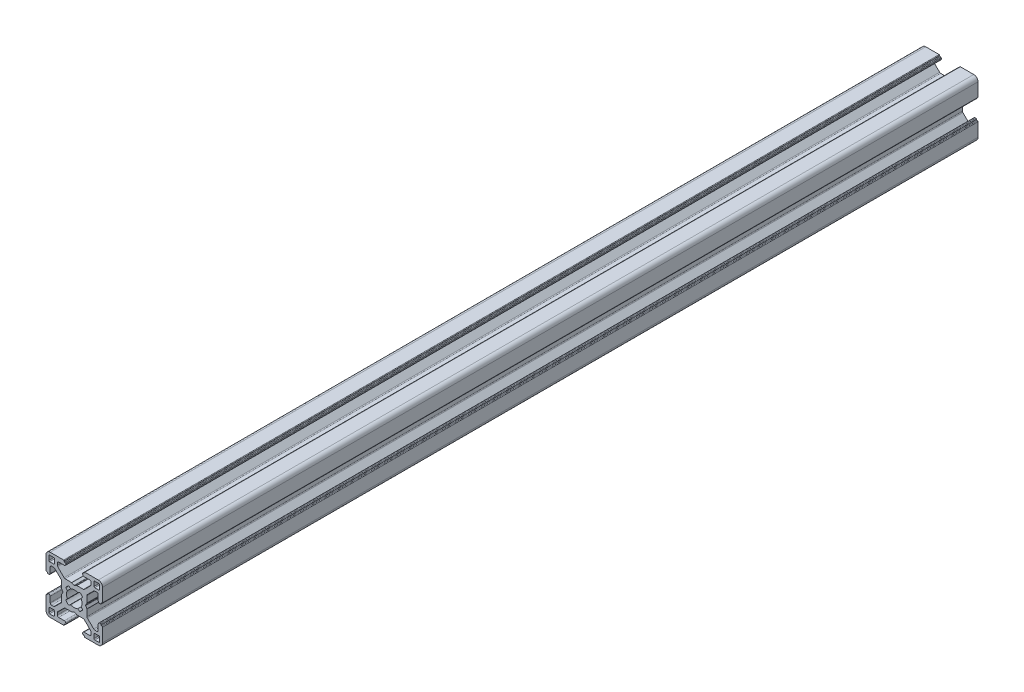
SolidWorks part; units mm, degrees
material "6063-O, Barra estrusa (SS)"
ref_plane "Piano frontale" through (0, 0, 0) normal (0, 0, 1) x (1, 0, 0)
ref_plane "Piano superiore" through (0, 0, 0) normal (0, 1, 0) x (1, 0, 0)
ref_plane "Piano destro" through (0, 0, 0) normal (1, 0, 0) x (0, 0, -1)
ref_plane "Piano1" through (0, 0, 100) normal (0, 0, 1) x (1, 0, 0)
sketch "Schizzo1" plane through (0, 0, 100) normal (0, 0, 1) x (1, 0, 0)
  line L0 (-1.9139, 2.9896) -> (-1.2582, 2.4453)
  line L1 (1.2582, 2.4453) -> (1.9139, 2.9896)
  line L2 (2.9922, 1.9099) -> (2.4453, 1.2582)
  line L3 (2.4453, -1.2582) -> (2.9922, -1.9099)
  line L4 (1.9139, -2.9896) -> (1.2582, -2.4453)
  line L5 (-1.2582, -2.4453) -> (-1.9139, -2.9896)
  line L6 (-2.9922, -1.9099) -> (-2.4453, -1.2582)
  line L7 (-2.4453, 1.2582) -> (-2.9922, 1.9099)
  line L8 (-9.3, 3) -> (-9, 3)
  line L9 (-8.5, 3.5) -> (-8.5, 5.5)
  line L10 (-8, 6) -> (-7.2678, 6)
  line L11 (-6.9142, 5.8536) -> (-4.6464, 3.5858)
  line L12 (-4.5, 3.2322) -> (-4.5, 0.9536)
  line L13 (-4.4732, 0.8536) -> (-4.0381, 0.1)
  line L14 (-4.0381, -0.1) -> (-4.4732, -0.8536)
  line L15 (-4.5, -0.9536) -> (-4.5, -3.2322)
  line L16 (-4.6464, -3.5858) -> (-6.9142, -5.8536)
  line L17 (-7.2678, -6) -> (-8, -6)
  line L18 (-8.5, -5.5) -> (-8.5, -3.5)
  line L19 (-9, -3) -> (-9.3, -3)
  line L20 (-9.5, -3.2) -> (-9.5, -3.35)
  line L21 (-9.7, -3.55) -> (-9.8, -3.55)
  line L22 (-10, -3.75) -> (-10, -8.5)
  line L23 (-8.5, -10) -> (-3.75, -10)
  line L24 (-3.55, -9.8) -> (-3.55, -9.7)
  line L25 (-3.35, -9.5) -> (-3.2, -9.5)
  line L26 (-3, -9.3) -> (-3, -9)
  line L27 (-3.5, -8.5) -> (-5.5, -8.5)
  line L28 (-6, -8) -> (-6, -7.2678)
  line L29 (-5.8536, -6.9142) -> (-3.5858, -4.6464)
  line L30 (-3.2322, -4.5) -> (-0.9536, -4.5)
  line L31 (-0.8536, -4.4732) -> (-0.1, -4.0381)
  line L32 (0.1, -4.0381) -> (0.8536, -4.4732)
  line L33 (0.9536, -4.5) -> (3.2322, -4.5)
  line L34 (3.5858, -4.6464) -> (5.8536, -6.9142)
  line L35 (6, -7.2678) -> (6, -8)
  line L36 (5.5, -8.5) -> (3.5, -8.5)
  line L37 (3, -9) -> (3, -9.3)
  line L38 (3.2, -9.5) -> (3.35, -9.5)
  line L39 (3.55, -9.7) -> (3.55, -9.8)
  line L40 (3.75, -10) -> (8.5, -10)
  line L41 (10, -8.5) -> (10, -3.75)
  line L42 (9.8, -3.55) -> (9.7, -3.55)
  line L43 (9.5, -3.35) -> (9.5, -3.2)
  line L44 (9.3, -3) -> (9, -3)
  line L45 (8.5, -3.5) -> (8.5, -5.5)
  line L46 (8, -6) -> (7.2678, -6)
  line L47 (6.9142, -5.8536) -> (4.6464, -3.5858)
  line L48 (4.5, -3.2322) -> (4.5, -0.9536)
  line L49 (4.4732, -0.8536) -> (4.0381, -0.1)
  line L50 (4.0381, 0.1) -> (4.4732, 0.8536)
  line L51 (4.5, 0.9536) -> (4.5, 3.2322)
  line L52 (4.6464, 3.5858) -> (6.9142, 5.8536)
  line L53 (7.2678, 6) -> (8, 6)
  line L54 (8.5, 5.5) -> (8.5, 3.5)
  line L55 (9, 3) -> (9.3, 3)
  line L56 (9.5, 3.2) -> (9.5, 3.35)
  line L57 (9.7, 3.55) -> (9.8, 3.55)
  line L58 (10, 3.75) -> (10, 8.5)
  line L59 (8.5, 10) -> (3.75, 10)
  line L60 (3.55, 9.8) -> (3.55, 9.7)
  line L61 (3.35, 9.5) -> (3.2, 9.5)
  line L62 (3, 9.3) -> (3, 9)
  line L63 (3.5, 8.5) -> (5.5, 8.5)
  line L64 (6, 8) -> (6, 7.2678)
  line L65 (5.8536, 6.9142) -> (3.5858, 4.6464)
  line L66 (3.2322, 4.5) -> (0.9536, 4.5)
  line L67 (0.8536, 4.4732) -> (0.1, 4.0381)
  line L68 (-0.1, 4.0381) -> (-0.8536, 4.4732)
  line L69 (-0.9536, 4.5) -> (-3.2322, 4.5)
  line L70 (-3.5858, 4.6464) -> (-5.8536, 6.9142)
  line L71 (-6, 7.2678) -> (-6, 8)
  line L72 (-5.5, 8.5) -> (-3.5, 8.5)
  line L73 (-3, 9) -> (-3, 9.3)
  line L74 (-3.2, 9.5) -> (-3.35, 9.5)
  line L75 (-3.55, 9.7) -> (-3.55, 9.8)
  line L76 (-3.75, 10) -> (-8.5, 10)
  line L77 (-10, 8.5) -> (-10, 3.75)
  line L78 (-9.8, 3.55) -> (-9.7, 3.55)
  line L79 (-9.5, 3.35) -> (-9.5, 3.2)
  line L80 (8.7, 7) -> (7.3, 7)
  line L81 (-7.3, 7) -> (-8.7, 7)
  line L82 (-7, 7.3) -> (-7, 8.7)
  line L83 (-7.3, 9) -> (-8.7, 9)
  line L84 (-9, 7.3) -> (-9, 8.7)
  line L85 (9, 7.3) -> (9, 8.7)
  line L86 (8.7, 9) -> (7.3, 9)
  line L87 (7, 7.3) -> (7, 8.7)
  line L88 (8.7, -9) -> (7.3, -9)
  line L89 (9, -8.7) -> (9, -7.3)
  line L90 (8.7, -7) -> (7.3, -7)
  line L91 (7, -8.7) -> (7, -7.3)
  line L92 (-7.3, -9) -> (-8.7, -9)
  line L93 (-7, -8.7) -> (-7, -7.3)
  line L94 (-7.3, -7) -> (-8.7, -7)
  line L95 (-9, -8.7) -> (-9, -7.3)
  arc A0 (-1.2582, 2.4453) -> (1.2582, 2.4453) centre (0, 0) cw
  arc A1 (1.9139, 2.9896) -> (2.9922, 1.9099) centre (0, 0) cw
  arc A2 (2.4453, 1.2582) -> (2.4453, -1.2582) centre (0, 0) cw
  arc A3 (2.9922, -1.9099) -> (1.9139, -2.9896) centre (0, 0) cw
  arc A4 (1.2582, -2.4453) -> (-1.2582, -2.4453) centre (0, 0) cw
  arc A5 (-1.9139, -2.9896) -> (-2.9922, -1.9099) centre (0, 0) cw
  arc A6 (-2.4453, -1.2582) -> (-2.4453, 1.2582) centre (0, 0) cw
  arc A7 (-2.9922, 1.9099) -> (-1.9139, 2.9896) centre (0, 0) cw
  arc A8 (-9.5, 3.2) -> (-9.3, 3) centre (-9.3, 3.2) ccw
  arc A9 (-9, 3) -> (-8.5, 3.5) centre (-9, 3.5) ccw
  arc A10 (-8.5, 5.5) -> (-8, 6) centre (-8, 5.5) cw
  arc A11 (-7.2678, 6) -> (-6.9142, 5.8536) centre (-7.2678, 5.5) cw
  arc A12 (-4.6464, 3.5858) -> (-4.5, 3.2322) centre (-5, 3.2322) cw
  arc A13 (-4.5, 0.9536) -> (-4.4732, 0.8536) centre (-4.3, 0.9536) ccw
  arc A14 (-4.0381, 0.1) -> (-4.0381, -0.1) centre (-4.2113, 0) cw
  arc A15 (-4.4732, -0.8536) -> (-4.5, -0.9536) centre (-4.3, -0.9536) ccw
  arc A16 (-4.5, -3.2322) -> (-4.6464, -3.5858) centre (-5, -3.2322) cw
  arc A17 (-6.9142, -5.8536) -> (-7.2678, -6) centre (-7.2678, -5.5) cw
  arc A18 (-8, -6) -> (-8.5, -5.5) centre (-8, -5.5) cw
  arc A19 (-8.5, -3.5) -> (-9, -3) centre (-9, -3.5) ccw
  arc A20 (-9.3, -3) -> (-9.5, -3.2) centre (-9.3, -3.2) ccw
  arc A21 (-9.5, -3.35) -> (-9.7, -3.55) centre (-9.7, -3.35) cw
  arc A22 (-9.8, -3.55) -> (-10, -3.75) centre (-9.8, -3.75) ccw
  arc A23 (-10, -8.5) -> (-8.5, -10) centre (-8.5, -8.5) ccw
  arc A24 (-3.75, -10) -> (-3.55, -9.8) centre (-3.75, -9.8) ccw
  arc A25 (-3.55, -9.7) -> (-3.35, -9.5) centre (-3.35, -9.7) cw
  arc A26 (-3.2, -9.5) -> (-3, -9.3) centre (-3.2, -9.3) ccw
  arc A27 (-3, -9) -> (-3.5, -8.5) centre (-3.5, -9) ccw
  arc A28 (-5.5, -8.5) -> (-6, -8) centre (-5.5, -8) cw
  arc A29 (-6, -7.2678) -> (-5.8536, -6.9142) centre (-5.5, -7.2678) cw
  arc A30 (-3.5858, -4.6464) -> (-3.2322, -4.5) centre (-3.2322, -5) cw
  arc A31 (-0.9536, -4.5) -> (-0.8536, -4.4732) centre (-0.9536, -4.3) ccw
  arc A32 (-0.1, -4.0381) -> (0.1, -4.0381) centre (0, -4.2113) cw
  arc A33 (0.8536, -4.4732) -> (0.9536, -4.5) centre (0.9536, -4.3) ccw
  arc A34 (3.2322, -4.5) -> (3.5858, -4.6464) centre (3.2322, -5) cw
  arc A35 (5.8536, -6.9142) -> (6, -7.2678) centre (5.5, -7.2678) cw
  arc A36 (6, -8) -> (5.5, -8.5) centre (5.5, -8) cw
  arc A37 (3.5, -8.5) -> (3, -9) centre (3.5, -9) ccw
  arc A38 (3, -9.3) -> (3.2, -9.5) centre (3.2, -9.3) ccw
  arc A39 (3.35, -9.5) -> (3.55, -9.7) centre (3.35, -9.7) cw
  arc A40 (3.55, -9.8) -> (3.75, -10) centre (3.75, -9.8) ccw
  arc A41 (8.5, -10) -> (10, -8.5) centre (8.5, -8.5) ccw
  arc A42 (10, -3.75) -> (9.8, -3.55) centre (9.8, -3.75) ccw
  arc A43 (9.7, -3.55) -> (9.5, -3.35) centre (9.7, -3.35) cw
  arc A44 (9.5, -3.2) -> (9.3, -3) centre (9.3, -3.2) ccw
  arc A45 (9, -3) -> (8.5, -3.5) centre (9, -3.5) ccw
  arc A46 (8.5, -5.5) -> (8, -6) centre (8, -5.5) cw
  arc A47 (7.2678, -6) -> (6.9142, -5.8536) centre (7.2678, -5.5) cw
  arc A48 (4.6464, -3.5858) -> (4.5, -3.2322) centre (5, -3.2322) cw
  arc A49 (4.5, -0.9536) -> (4.4732, -0.8536) centre (4.3, -0.9536) ccw
  arc A50 (4.0381, -0.1) -> (4.0381, 0.1) centre (4.2113, 0) cw
  arc A51 (4.4732, 0.8536) -> (4.5, 0.9536) centre (4.3, 0.9536) ccw
  arc A52 (4.5, 3.2322) -> (4.6464, 3.5858) centre (5, 3.2322) cw
  arc A53 (6.9142, 5.8536) -> (7.2678, 6) centre (7.2678, 5.5) cw
  arc A54 (8, 6) -> (8.5, 5.5) centre (8, 5.5) cw
  arc A55 (8.5, 3.5) -> (9, 3) centre (9, 3.5) ccw
  arc A56 (9.3, 3) -> (9.5, 3.2) centre (9.3, 3.2) ccw
  arc A57 (9.5, 3.35) -> (9.7, 3.55) centre (9.7, 3.35) cw
  arc A58 (9.8, 3.55) -> (10, 3.75) centre (9.8, 3.75) ccw
  arc A59 (10, 8.5) -> (8.5, 10) centre (8.5, 8.5) ccw
  arc A60 (3.75, 10) -> (3.55, 9.8) centre (3.75, 9.8) ccw
  arc A61 (3.55, 9.7) -> (3.35, 9.5) centre (3.35, 9.7) cw
  arc A62 (3.2, 9.5) -> (3, 9.3) centre (3.2, 9.3) ccw
  arc A63 (3, 9) -> (3.5, 8.5) centre (3.5, 9) ccw
  arc A64 (5.5, 8.5) -> (6, 8) centre (5.5, 8) cw
  arc A65 (6, 7.2678) -> (5.8536, 6.9142) centre (5.5, 7.2678) cw
  arc A66 (3.5858, 4.6464) -> (3.2322, 4.5) centre (3.2322, 5) cw
  arc A67 (0.9536, 4.5) -> (0.8536, 4.4732) centre (0.9536, 4.3) ccw
  arc A68 (0.1, 4.0381) -> (-0.1, 4.0381) centre (0, 4.2113) cw
  arc A69 (-0.8536, 4.4732) -> (-0.9536, 4.5) centre (-0.9536, 4.3) ccw
  arc A70 (-3.2322, 4.5) -> (-3.5858, 4.6464) centre (-3.2322, 5) cw
  arc A71 (-5.8536, 6.9142) -> (-6, 7.2678) centre (-5.5, 7.2678) cw
  arc A72 (-6, 8) -> (-5.5, 8.5) centre (-5.5, 8) cw
  arc A73 (-3.5, 8.5) -> (-3, 9) centre (-3.5, 9) ccw
  arc A74 (-3, 9.3) -> (-3.2, 9.5) centre (-3.2, 9.3) ccw
  arc A75 (-3.35, 9.5) -> (-3.55, 9.7) centre (-3.35, 9.7) cw
  arc A76 (-3.55, 9.8) -> (-3.75, 10) centre (-3.75, 9.8) ccw
  arc A77 (-8.5, 10) -> (-10, 8.5) centre (-8.5, 8.5) ccw
  arc A78 (-10, 3.75) -> (-9.8, 3.55) centre (-9.8, 3.75) ccw
  arc A79 (-9.7, 3.55) -> (-9.5, 3.35) centre (-9.7, 3.35) cw
  arc A80 (-8.7, 7) -> (-9, 7.3) centre (-8.7, 7.3) cw
  arc A81 (-7, 8.7) -> (-7.3, 9) centre (-7.3, 8.7) ccw
  arc A82 (-7.3, 7) -> (-7, 7.3) centre (-7.3, 7.3) ccw
  arc A83 (-8.7, 9) -> (-9, 8.7) centre (-8.7, 8.7) ccw
  arc A84 (7.3, 7) -> (7, 7.3) centre (7.3, 7.3) cw
  arc A85 (9, 8.7) -> (8.7, 9) centre (8.7, 8.7) ccw
  arc A86 (8.7, 7) -> (9, 7.3) centre (8.7, 7.3) ccw
  arc A87 (7.3, 9) -> (7, 8.7) centre (7.3, 8.7) ccw
  arc A88 (7.3, -9) -> (7, -8.7) centre (7.3, -8.7) cw
  arc A89 (9, -7.3) -> (8.7, -7) centre (8.7, -7.3) ccw
  arc A90 (8.7, -9) -> (9, -8.7) centre (8.7, -8.7) ccw
  arc A91 (7.3, -7) -> (7, -7.3) centre (7.3, -7.3) ccw
  arc A92 (-8.7, -9) -> (-9, -8.7) centre (-8.7, -8.7) cw
  arc A93 (-7, -7.3) -> (-7.3, -7) centre (-7.3, -7.3) ccw
  arc A94 (-7.3, -9) -> (-7, -8.7) centre (-7.3, -8.7) ccw
  arc A95 (-8.7, -7) -> (-9, -7.3) centre (-8.7, -7.3) ccw
  dimension "D1" = 0.3
  dimension "D2" = 1
  dimension "D3" = 1
  dimension "D4" = 1
  dimension "D7" = 1
  dimension "D8" = 1
  dimension "D9" = 1
  dimension "D10" = 1
  dimension "D5" = 2
  dimension "D6" = 2
extrude "Estrusione-Estrusione1" add sketch "Schizzo1" against normal blind 310
